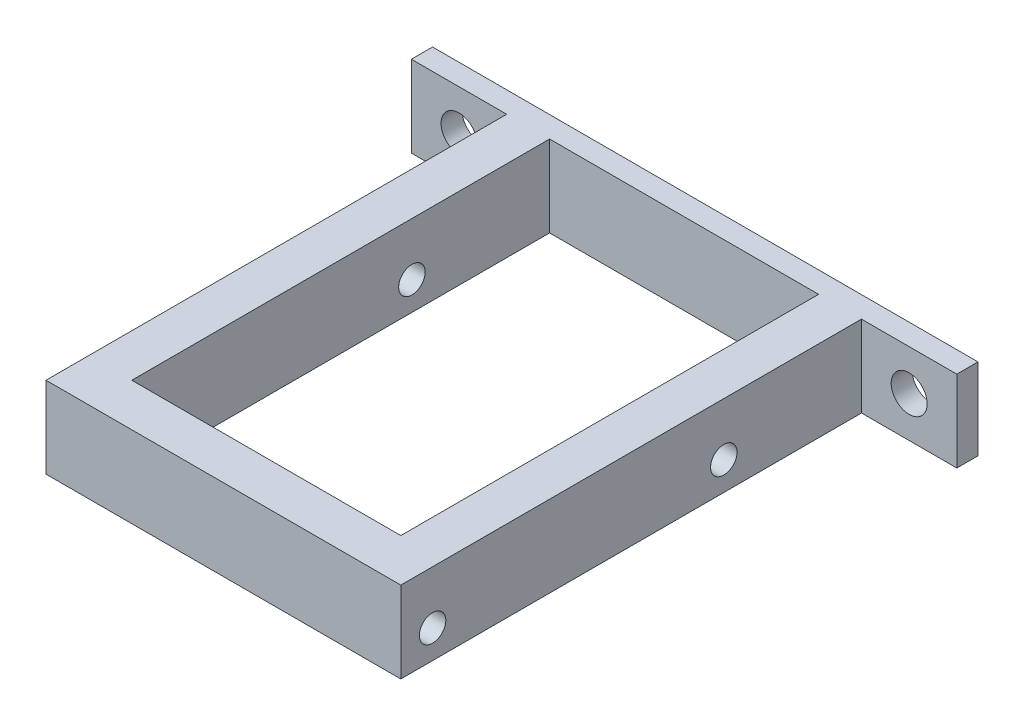
SolidWorks part; units mm, degrees
ref_plane "Front Plane" through (0, 0, 0) normal (0, 0, 1) x (1, 0, 0)
ref_plane "Top Plane" through (0, 0, 0) normal (0, 1, 0) x (1, 0, 0)
ref_plane "Right Plane" through (0, 0, 0) normal (1, 0, 0) x (0, 0, -1)
sketch "Sketch25" plane through (0, 0, 0) normal (0, 1, 0) x (1, 0, 0)
  line L1 (25.75, 28.75) -> (-25.75, 28.75)
  line L2 (25.75, 28.75) -> (25.75, 26.75)
  line L3 (25.75, 26.75) -> (16.75, 26.75)
  line L4 (-25.75, 28.75) -> (-25.75, 26.75)
  line L5 (16.75, -16.75) -> (-16.75, -16.75)
  line L6 (16.75, 26.75) -> (16.75, -16.75)
  line L8 (12.7, 26.75) -> (12.7, -12.7)
  line L9 (-16.75, 26.75) -> (-25.75, 26.75)
  line L10 (12.7, 26.75) -> (-12.7, 26.75)
  line L11 (-16.75, 26.75) -> (-16.75, -16.75)
  line L13 (-12.7, 26.75) -> (-12.7, -12.7)
  line L16 (-12.7, -12.7) -> (12.7, -12.7)
  point P7 (0, -16.75)
  point P14 (0, -12.7)
  dimension "D1" = 9
  dimension "D2" = 9
  dimension "D3" = 25.4
  dimension "D4" = 43.5
  dimension "D5" = 51.5
  dimension "D6" = 2
  dimension "D7" = 4.05
extrude "Boss-Extrude5" add sketch "Sketch25" against normal blind 7.68 separate body
hole_wizard "M3x0.5 Tapped Hole2" positions "3DSketch4" profile "Sketch6" tap size "M3x0.5" standard "ANSI Metric"
sketch3d "3DSketch4"
  line L3 (16.75, -7.68, 16.75) -> (16.75, 0, 16.75) construction
  line L4 (16.75, -7.68, 16.75) -> (16.75, -7.68, -26.75) construction
  point P13 (16.75, -5, 13.75)
  point P15 (16.75, -5, -13.75)
  point P17 (-16.75, -5, -13.75)
  point P26 (-16.75, -5, 13.75)
  point P29 (0, 0, 0)
  point P30 (0, 0, 0)
  dimension "D5" = 3
  dimension "D6" = 27.5
  dimension "D7" = 2.68
sketch "Sketch6" plane through (16.75, -5, 13.75) normal (0, 1, 0) x (0, 0, -1)
  line L0 (0, 0) -> (0, 8.3711)
  line L1 (0, 8.3711) -> (1.25, 7.62)
  line L2 (1.25, 7.62) -> (1.25, 0)
  line L5 (1.25, 0) -> (0, 0)
  line L10 (0, 8.3711) -> (-1.25, 7.62) construction
  line L11 (0, -6.35) -> (0, 107.95) construction
  point P3 (0, 0)
  dimension "Tap Drill Dia." = 2.5
  dimension "Tap Drill Depth" = 7.62
  dimension "Drill Angle" = 118
hole_wizard "M3 Clearance Hole3" positions "3DSketch7" profile "Sketch23" hole size "M3" standard "ANSI Metric" end condition through all
sketch3d "3DSketch7"
  line L5 (16.75, 0, -26.75) -> (25.75, 0, -26.75) construction
  line L6 (25.75, -7.68, -26.75) -> (25.75, 0, -26.75) construction
  line L8 (-25.75, -7.68, -26.75) -> (-16.75, -7.68, -26.75) construction
  point P0 (21.25, -3.84, -26.75)
  point P2 (-21.25, -3.84, -26.75)
  point P13 (30.8002, -8.3118, -16.75)
  point P14 (0, 0, 0)
  point P15 (0, 0, 0)
  point P16 (0, 0, 0)
  point P17 (0, 0, 0)
  point P18 (0, 0, 0)
  point P22 (0, 0, 0)
  point P23 (29.5998, -6.0888, -26.75)
  point P24 (0, 0, 0)
  point P27 (21.25, 0, -26.75)
  point P28 (0, 0, 0)
  point P31 (25.75, -3.84, -26.75)
  point P32 (0, 0, 0)
  point P38 (-21.25, -7.68, -26.75)
sketch "Sketch23" plane through (21.25, -3.84, -26.75) normal (1, 0, 0) x (0, -1, 0)
  line L0 (0, 0) -> (0, 2)
  line L1 (0, 2) -> (1.7, 2)
  line L2 (1.7, 2) -> (1.7, 0)
  line L5 (1.7, 0) -> (0, 0)
  line L11 (0, -6.35) -> (0, 107.95) construction
  dimension "Thru Hole Dia." = 3.4
  dimension "Thru Hole Depth" = 2
